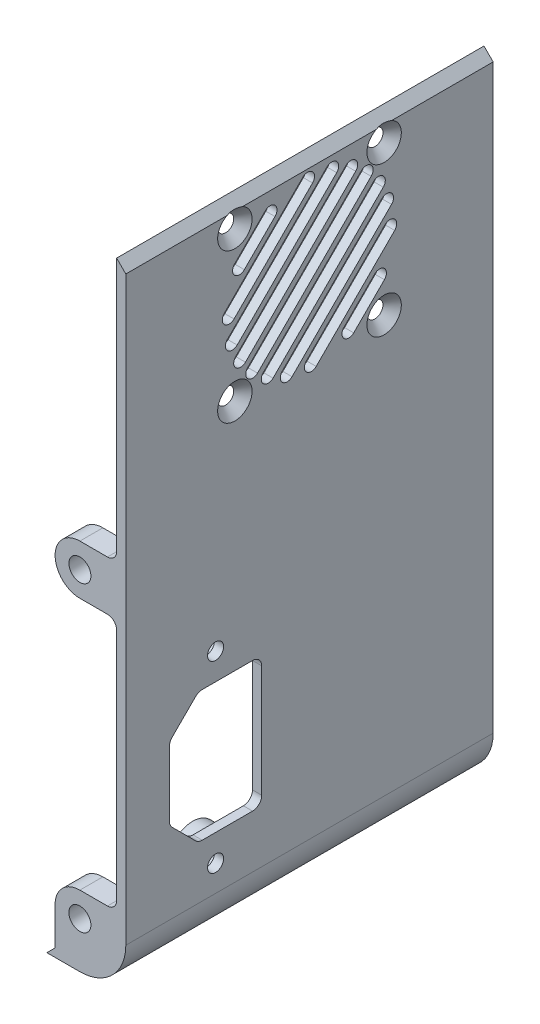
SolidWorks part; units mm, degrees
ref_plane "Piano frontale" through (0, 0, 0) normal (0, 0, 1) x (1, 0, 0)
ref_plane "Piano superiore" through (0, 0, 0) normal (0, 1, 0) x (1, 0, 0)
ref_plane "Piano destro" through (0, 0, 0) normal (1, 0, 0) x (0, 0, -1)
sketch "Schizzo1" plane through (0, 0, 0) normal (0, 0, 1) x (1, 0, 0)
  line L0 (0, 0) -> (170, 0)
  line L1 (170, 0) -> (170, 150)
  line L2 (170, 150) -> (56.5685, 150)
  line L3 (56.5685, 150) -> (0, 93.4315)
  line L4 (0, 93.4315) -> (0, 0)
  dimension "D1" = 45
  dimension "D2" = 170
  dimension "D3" = 150
  dimension "D4" = 80
extrude "Estrusione-Sottile1" add sketch "Schizzo1" along normal blind 80 thin thin type one direction wall 2
ref_plane "middle" through (0, 0, 40) normal (0, 0, -1) x (-1, 0, 0)
sketch "Schizzo2" plane through (-48.1299, 48.1299, 0) normal (-0.7071, 0.7071, 0) x (0, 0, 1)
  line L0 (0, 146.8944) -> (80, 65.2376) construction
  line L2 (13, 88.316) -> (67, 88.316)
  line L3 (13, 88.316) -> (13, 123.816)
  line L4 (13, 123.816) -> (67, 123.816)
  line L5 (67, 88.316) -> (67, 123.816)
  line L6 (13, 88.316) -> (67, 123.816) construction
  line L7 (13, 123.816) -> (67, 88.316) construction
  point P4 (40, 106.066)
  dimension "D1" = 54
  dimension "D2" = 35.5
extrude "Taglio-Estrusione1" cut sketch "Schizzo2" against normal blind 10
fillet "Raccordo1" radius 10 10 edges at (170, 150, 40) (56.5685, 150, 40) (0, 93.4315, 40) (0, 0, 40) (170, 0, 40) (-2, 94.2599, 40) (172, 152, 40) (172, -2, 40) (-2, -2, 40) (55.7401, 152, 40)
sketch "Schizzo3" plane through (-48.1299, 48.1299, 0) normal (-0.7071, 0.7071, 0) x (0, 0, 1)
  line L0 (64.31, 108.816) -> (15.69, 108.816) construction
  line L1 (64.31, 97.666) -> (64.31, 119.966) construction
  line L2 (15.69, 119.966) -> (15.69, 97.666) construction
  line L3 (69, 86.316) -> (11, 86.316)
  line L4 (15.69, 96.666) -> (64.31, 96.666)
  line L5 (15.69, 96.666) -> (15.69, 120.966)
  line L6 (15.69, 120.966) -> (64.31, 120.966)
  line L7 (64.31, 96.666) -> (64.31, 120.966)
  line L8 (15.69, 96.666) -> (64.31, 120.966) construction
  line L9 (15.69, 120.966) -> (64.31, 96.666) construction
  line L10 (67, 123.816) -> (13, 123.816) construction
  line L11 (67, 123.816) -> (67, 88.316) construction
  line L12 (67, 88.316) -> (13, 88.316) construction
  line L13 (13, 123.816) -> (13, 88.316) construction
  line L14 (11, 125.816) -> (11, 86.316)
  line L15 (69, 125.816) -> (11, 125.816)
  line L16 (69, 125.816) -> (69, 86.316)
  point P6 (40, 108.816)
  dimension "D1" = 2
extrude "Estrusione-Estrusione1" add sketch "Schizzo3" along normal blind 1
fillet "Raccordo2" radius 2 8 edges at (12.5511, 109.5181, 11) (40.4819, 137.4489, 11) (40.4819, 137.4489, 69) (12.5511, 109.5181, 69) (37.0524, 134.0194, 64.31) (19.8697, 116.8367, 15.69) (19.8697, 116.8367, 64.31) (37.0524, 134.0194, 15.69)
fillet "Raccordo3" radius 0.5 16 edges at (12.6118, 110.2859, 11.5858) (26.163, 123.837, 11) (39.7141, 137.3882, 11.5858) (40.1283, 137.8024, 40) (39.7141, 137.3882, 68.4142) (26.163, 123.837, 69) (12.6118, 110.2859, 68.4142) (13.3189, 109.5788, 11.5858) (26.8701, 123.1299, 11) (40.4212, 136.6811, 11.5858) (40.8354, 137.0953, 40) (40.4212, 136.6811, 68.4142) (26.8701, 123.1299, 69) (13.3189, 109.5788, 68.4142) (12.1976, 109.8717, 40) (12.9047, 109.1646, 40)
chamfer "Smusso1" distance 0.75 angle 69 8 edges at (36.6988, 134.3729, 40) (36.2846, 133.9587, 16.2758) (36.2846, 133.9587, 63.7242) (28.1075, 125.7816, 15.69) (28.1075, 125.7816, 64.31) (19.9304, 117.6045, 16.2758) (19.9304, 117.6045, 63.7242) (19.5161, 117.1902, 40) first distance on face at (37.0524, 134.0194, 40) first distance on face at (36.4917, 133.4587, 16.4829) first distance on face at (36.4917, 133.4587, 63.5171) first distance on face at (28.461, 125.428, 15.69) first distance on face at (28.461, 125.428, 64.31) first distance on face at (20.4304, 117.3974, 16.4829) first distance on face at (20.4304, 117.3974, 63.5171) first distance on face at (19.8697, 116.8367, 40)
sketch "Schizzo4" plane through (-48.837, 48.837, 0) normal (-0.7071, 0.7071, 0) x (0.7071, 0.7071, 0)
  line L0 (89.316, -11.5) -> (89.316, -68.5) construction
  line L1 (123.816, -11.5) -> (88.316, -11.5) construction
  line L2 (88.316, -68.5) -> (123.816, -68.5) construction
  line L3 (86.816, -13) -> (86.816, -67) construction
  text T0 "Soldering station V3" font "Eras Bold ITC" height 3
  dimension "D1" = 2.5
extrude "Taglio-Estrusione2" cut sketch "Schizzo4" against normal blind 0.75
sketch "Schizzo5" plane through (0, 0, 80) normal (0, 0, 1) x (1, 0, 0)
  line L0 (156.6, 142) -> (156.6, 150)
  line L1 (160, 150) -> (60.7107, 150) construction
  line L2 (162, 136.6) -> (170, 136.6)
  line L3 (170, 10) -> (170, 140) construction
  line L4 (160, 150) -> (156.6, 150)
  line L5 (170, 136.6) -> (170, 140)
  line L6 (162, 13.4) -> (170, 13.4)
  line L7 (170, 13.4) -> (170, 10)
  line L8 (156.6, 8) -> (156.6, 0)
  line L9 (156.6, 0) -> (160, 0)
  line L10 (13.4, 8) -> (13.4, 0)
  line L11 (10, 0) -> (160, 0) construction
  line L12 (13.4, 0) -> (10, 0)
  line L13 (8, 13.4) -> (0, 13.4)
  line L14 (0, 89.2893) -> (0, 10) construction
  line L15 (0, 13.4) -> (0, 10)
  line L16 (6.1615, 99.593) -> (11.8184, 93.9361)
  line L17 (53.6396, 147.0711) -> (2.9289, 96.3604) construction
  line L18 (8, 84.7177) -> (0, 84.7177)
  line L19 (0, 84.7177) -> (0, 89.2893)
  line L20 (6.1615, 99.593) -> (2.9289, 96.3604)
  line L21 (65.2823, 142) -> (65.2823, 150)
  line L22 (65.2823, 150) -> (60.7107, 150)
  line L23 (50.407, 143.8385) -> (56.0639, 138.1816)
  line L24 (50.407, 143.8385) -> (53.6396, 147.0711)
  line L25 (78.4818, 8) -> (78.4818, 0)
  line L26 (89.2818, 8) -> (89.2818, 0)
  line L27 (89.2818, 0) -> (78.4818, 0)
  line L28 (162, 79.2294) -> (170, 79.2294)
  line L29 (162, 68.4294) -> (170, 68.4294)
  line L30 (170, 79.2294) -> (170, 68.4294)
  circle A0 centre (162, 142) radius 2.4
  arc A1 (156.6, 142) -> (162, 136.6) centre (162, 142) ccw
  arc A2 (170, 140) -> (160, 150) centre (160, 140) ccw construction
  arc A3 (170, 140) -> (160, 150) centre (160, 140) ccw
  circle A4 centre (162, 8) radius 2.4
  arc A5 (162, 13.4) -> (156.6, 8) centre (162, 8) ccw
  arc A6 (160, 0) -> (170, 10) centre (160, 10) ccw construction
  arc A7 (160, 0) -> (170, 10) centre (160, 10) ccw
  circle A8 centre (8, 8) radius 2.4
  arc A10 (13.4, 8) -> (8, 13.4) centre (8, 8) ccw
  arc A11 (0, 10) -> (10, 0) centre (10, 10) ccw construction
  arc A12 (0, 10) -> (10, 0) centre (10, 10) ccw
  circle A13 centre (8, 90.1177) radius 2.4
  arc A14 (8, 84.7177) -> (11.8184, 93.9361) centre (8, 90.1177) ccw
  arc A15 (2.9289, 96.3604) -> (0, 89.2893) centre (10, 89.2893) ccw construction
  arc A16 (2.9289, 96.3604) -> (0, 89.2893) centre (10, 89.2893) ccw
  circle A17 centre (59.8823, 142) radius 2.4
  arc A18 (56.0639, 138.1816) -> (65.2823, 142) centre (59.8823, 142) ccw
  arc A19 (60.7107, 150) -> (53.6396, 147.0711) centre (60.7107, 140) ccw construction
  arc A20 (60.7107, 150) -> (53.6396, 147.0711) centre (60.7107, 140) ccw
  circle A21 centre (83.8818, 8) radius 2.4
  arc A22 (89.2818, 8) -> (78.4818, 8) centre (83.8818, 8) ccw
  circle A23 centre (162, 73.8294) radius 2.4
  arc A24 (162, 79.2294) -> (162, 68.4294) centre (162, 73.8294) ccw
  dimension "D1" = 4.8
  dimension "D2" = 3
extrude "Estrusione-Estrusione2" add sketch "Schizzo5" against normal blind 5
fillet "Raccordo4" radius 2 14 edges at (6.1615, 99.593, 77.5) (0, 84.7177, 77.5) (0, 13.4, 77.5) (13.4, 0, 77.5) (78.4818, 0, 77.5) (89.2818, 0, 77.5) (156.6, 0, 77.5) (170, 13.4, 77.5) (170, 68.4294, 77.5) (170, 79.2294, 77.5) (170, 136.6, 77.5) (156.6, 150, 77.5) (50.407, 143.8385, 77.5) (65.2823, 150, 77.5)
mirror "Specchia1" about plane through (0, 0, 40) normal (0, 0, -1) of "Estrusione-Estrusione2", "Raccordo4"
sketch "Schizzo6" plane through (-2, 0, 0) normal (-1, 0, 0) x (0, 0, 1)
  line L0 (40, 90.1177) -> (40, 8) construction
  line L1 (80, 90.1177) -> (0, 90.1177) construction
  line L2 (0, 8) -> (80, 8) construction
  line L4 (11, 13.25) -> (24, 13.25)
  line L5 (11, 13.25) -> (11, 32.75)
  line L6 (11, 32.75) -> (24, 32.75)
  line L7 (24, 13.25) -> (24, 32.75)
  line L8 (11, 13.25) -> (24, 32.75) construction
  line L9 (11, 32.75) -> (24, 13.25) construction
  circle A0 centre (40, 65.1177) radius 3.25
  circle A1 centre (40, 23) radius 6
  point P10 (17.5, 23)
  dimension "D2" = 6.5
  dimension "D4" = 12
  dimension "D1" = 25
  dimension "D3" = 15
  dimension "D5" = 13
  dimension "D6" = 19.5
  dimension "D7" = 22.5
extrude "Taglio-Estrusione3" cut sketch "Schizzo6" against normal blind 5
sketch "Schizzo7" plane through (0, 0, 0) normal (1, 0, 0) x (0, 0, -1)
  line L0 (-71.85, 34.17) -> (-71.85, 25.83) construction
  line L1 (-72.205, 34.17) -> (-71.495, 34.17) construction
  line L2 (-71.495, 25.83) -> (-72.205, 25.83) construction
  line L3 (-71.495, 25.53) -> (-72.205, 25.53) construction
  line L4 (-70.245, 33.22) -> (-70.245, 26.78) construction
  line L5 (-71.495, 25.53) -> (-72.205, 25.53) construction
  line L6 (-71.495, 34.47) -> (-72.205, 34.47) construction
  line L7 (-72.205, 34.47) -> (-71.495, 34.47) construction
  line L8 (-73.455, 33.22) -> (-73.455, 26.78) construction
  line L9 (-71.495, 25.03) -> (-72.205, 25.03)
  line L10 (-73.955, 33.22) -> (-73.955, 26.78)
  line L11 (-71.495, 34.97) -> (-72.205, 34.97)
  line L12 (-69.745, 33.22) -> (-69.745, 26.78)
  arc A0 (-70.245, 26.78) -> (-71.495, 25.53) centre (-71.495, 26.78) cw construction
  arc A1 (-70.245, 33.22) -> (-71.495, 34.47) centre (-71.495, 33.22) ccw construction
  arc A2 (-73.455, 33.22) -> (-72.205, 34.47) centre (-72.205, 33.22) cw construction
  arc A3 (-73.455, 26.78) -> (-72.205, 25.53) centre (-72.205, 26.78) ccw construction
  arc A4 (-73.955, 26.78) -> (-72.205, 25.03) centre (-72.205, 26.78) ccw
  arc A5 (-73.955, 33.22) -> (-72.205, 34.97) centre (-72.205, 33.22) cw
  arc A6 (-69.745, 33.22) -> (-71.495, 34.97) centre (-71.495, 33.22) ccw
  arc A7 (-69.745, 26.78) -> (-71.495, 25.03) centre (-71.495, 26.78) cw
  circle A8 centre (-69.35, 43) radius 2.25
  circle A9 centre (-69.35, 54) radius 2.25
  point P19 (-71.85, 25.53)
  point P28 (-71.85, 34.47)
  dimension "D2" = 4.5
  dimension "D1" = 0.5
extrude "Taglio-Estrusione4" cut sketch "Schizzo7" against normal blind 5
sketch "Schizzo8" plane through (0, 0, 0) normal (1, 0, 0) x (0, 0, -1)
  line L0 (-72.205, 25.03) -> (-71.495, 25.03) construction
  line L1 (-73.955, 33.22) -> (-73.955, 26.78) construction
  line L2 (-71.495, 34.97) -> (-72.205, 34.97) construction
  line L3 (-69.745, 26.78) -> (-69.745, 33.22) construction
  line L4 (-72.205, 25.03) -> (-71.495, 25.03)
  line L5 (-73.955, 33.22) -> (-73.955, 26.78)
  line L6 (-71.495, 34.97) -> (-72.205, 34.97)
  line L7 (-69.745, 26.78) -> (-69.745, 33.22)
  line L8 (-71.495, 36.47) -> (-72.205, 36.47)
  line L9 (-75.455, 33.22) -> (-75.455, 26.78)
  line L10 (-72.205, 23.53) -> (-71.495, 23.53)
  line L11 (-68.245, 26.78) -> (-68.245, 33.22)
  arc A0 (-71.495, 25.03) -> (-69.745, 26.78) centre (-71.495, 26.78) ccw construction
  arc A1 (-73.955, 26.78) -> (-72.205, 25.03) centre (-72.205, 26.78) ccw construction
  arc A2 (-72.205, 34.97) -> (-73.955, 33.22) centre (-72.205, 33.22) ccw construction
  arc A3 (-69.745, 33.22) -> (-71.495, 34.97) centre (-71.495, 33.22) ccw construction
  arc A4 (-71.495, 25.03) -> (-69.745, 26.78) centre (-71.495, 26.78) ccw
  arc A5 (-73.955, 26.78) -> (-72.205, 25.03) centre (-72.205, 26.78) ccw
  arc A6 (-72.205, 34.97) -> (-73.955, 33.22) centre (-72.205, 33.22) ccw
  arc A7 (-69.745, 33.22) -> (-71.495, 34.97) centre (-71.495, 33.22) ccw
  arc A8 (-68.245, 33.22) -> (-71.495, 36.47) centre (-71.495, 33.22) ccw
  arc A9 (-72.205, 36.47) -> (-75.455, 33.22) centre (-72.205, 33.22) ccw
  arc A10 (-75.455, 26.78) -> (-72.205, 23.53) centre (-72.205, 26.78) ccw
  arc A11 (-71.495, 23.53) -> (-68.245, 26.78) centre (-71.495, 26.78) ccw
  dimension "D1" = 1.5
extrude "Estrusione-Estrusione3" add sketch "Schizzo8" along normal up to surface (2 mm away)
chamfer "Smusso2" distance 2 angle 45 8 edges at (-2, 30, 73.955) (-2, 25.5426, 73.4424) (-2, 34.4574, 73.4424) (-2, 25.03, 71.85) (-2, 34.97, 71.85) (-2, 25.5426, 70.2576) (-2, 34.4574, 70.2576) (-2, 30, 69.745)
sketch "Schizzo9" plane through (170, 0, 0) normal (-1, 0, 0) x (0, 0, 1)
  line L0 (52.4, 47.4) -> (63.3787, 47.4) construction
  line L1 (64.4393, 46.9607) -> (69.5607, 41.8393) construction
  line L2 (70, 40.7787) -> (70, 26.6213) construction
  line L3 (69.5607, 25.5607) -> (64.4393, 20.4393) construction
  line L4 (63.3787, 20) -> (52.4, 20) construction
  line L5 (50.9, 21.5) -> (50.9, 45.9) construction
  line L6 (50.9, 45.9) -> (50.9, 21.5) construction
  line L7 (52.4, 47.9) -> (63.3787, 47.9)
  line L8 (64.7929, 47.3142) -> (69.9142, 42.1929)
  line L9 (70.5, 40.7787) -> (70.5, 26.6213)
  line L10 (69.9142, 25.2071) -> (64.7929, 20.0858)
  line L11 (63.3787, 19.5) -> (52.4, 19.5)
  line L12 (50.4, 21.5) -> (50.4, 45.9)
  line L13 (40, 140) -> (40, 135) construction
  line L14 (75, 140) -> (5, 140) construction
  line L15 (40, 135) -> (40, 95) construction
  line L17 (23.75, 98.75) -> (56.25, 98.75) construction
  line L18 (23.75, 98.75) -> (23.75, 131.25) construction
  line L19 (23.75, 131.25) -> (56.25, 131.25) construction
  line L20 (56.25, 98.75) -> (56.25, 131.25) construction
  line L21 (23.75, 98.75) -> (56.25, 131.25) construction
  line L22 (23.75, 131.25) -> (56.25, 98.75) construction
  arc A0 (50.9, 21.5) -> (52.4, 20) centre (52.4, 21.5) ccw construction
  arc A1 (52.4, 20) -> (50.9, 21.5) centre (52.4, 21.5) cw construction
  arc A2 (63.3787, 20) -> (64.4393, 20.4393) centre (63.3787, 21.5) ccw construction
  arc A3 (69.5607, 25.5607) -> (70, 26.6213) centre (68.5, 26.6213) ccw construction
  arc A4 (70, 40.7787) -> (69.5607, 41.8393) centre (68.5, 40.7787) ccw construction
  arc A5 (64.4393, 46.9607) -> (63.3787, 47.4) centre (63.3787, 45.9) ccw construction
  arc A6 (52.4, 47.4) -> (50.9, 45.9) centre (52.4, 45.9) ccw construction
  arc A7 (64.7929, 47.3142) -> (63.3787, 47.9) centre (63.3787, 45.9) ccw
  arc A8 (70.5, 40.7787) -> (69.9142, 42.1929) centre (68.5, 40.7787) ccw
  arc A9 (69.9142, 25.2071) -> (70.5, 26.6213) centre (68.5, 26.6213) ccw
  arc A10 (63.3787, 19.5) -> (64.7929, 20.0858) centre (63.3787, 21.5) ccw
  arc A11 (52.4, 19.5) -> (50.4, 21.5) centre (52.4, 21.5) cw
  arc A12 (52.4, 47.9) -> (50.4, 45.9) centre (52.4, 45.9) ccw
  circle A13 centre (60.45, 53.7) radius 1.75
  circle A14 centre (60.45, 13.7) radius 1.75
  circle A15 centre (56.25, 131.25) radius 1.75
  circle A16 centre (23.75, 131.25) radius 1.75
  circle A17 centre (23.75, 98.75) radius 1.75
  circle A18 centre (56.25, 98.75) radius 1.75
  point P62 (40, 115)
  dimension "D6" = 3.5
  dimension "D7" = 3.5
  dimension "D2" = 5
  dimension "D3" = 40
  dimension "D4" = 32.5
  dimension "D5" = 32.5
  dimension "D1" = 0.5
extrude "Taglio-Estrusione5" cut sketch "Schizzo9" against normal blind 10
sketch "Schizzo10" plane through (170, 0, 0) normal (-1, 0, 0) x (0, 0, 1)
  circle A0 centre (60.45, 53.7) radius 2.4
  circle A1 centre (60.45, 53.7) radius 5.4
  circle A2 centre (60.45, 13.7) radius 2.4
  circle A3 centre (60.45, 13.7) radius 5.4
  dimension "D1" = 4.8
  dimension "D2" = 3
extrude "Estrusione-Estrusione4" add sketch "Schizzo10" along normal blind 3
sketch "Schizzo11" plane through (172, 0, 0) normal (1, 0, 0) x (0, 0, -1)
  line L0 (-56.25, 131.25) -> (-23.75, 98.75) construction
  line L1 (-55.256, 123.5735) -> (-48.5735, 130.256) construction
  line L2 (-56.3166, 124.6342) -> (-49.6342, 131.3166)
  line L3 (-54.1953, 122.5129) -> (-47.5129, 129.1953)
  line L4 (-57.4956, 115.3942) -> (-40.3942, 132.4956) construction
  line L5 (-58.5562, 116.4549) -> (-41.4549, 133.5562)
  line L6 (-56.4349, 114.3336) -> (-39.3336, 131.4349)
  line L7 (-56.8113, 110.1388) -> (-35.1388, 131.8113) construction
  line L8 (-57.8719, 111.1995) -> (-36.1995, 132.8719)
  line L9 (-55.7506, 109.0782) -> (-34.0782, 130.7506)
  line L10 (-55.0091, 106.0013) -> (-31.0013, 130.0091) construction
  line L11 (-56.0698, 107.062) -> (-32.062, 131.0698)
  line L12 (-53.9484, 104.9406) -> (-29.9406, 128.9484)
  line L13 (-52.3744, 102.6256) -> (-27.6256, 127.3744) construction
  line L14 (-53.435, 103.6863) -> (-28.6863, 128.435)
  line L15 (-51.3137, 101.565) -> (-26.565, 126.3137)
  line L16 (-53.435, 128.435) -> (-50.2284, 131.6416) construction
  line L17 (-23.75, 131.25) -> (-56.25, 98.75) construction
  line L18 (-48.9987, 99.9909) -> (-24.9909, 123.9987) construction
  line L19 (-47.938, 98.9302) -> (-23.9302, 122.938)
  line L20 (-50.0594, 101.0516) -> (-26.0516, 125.0594)
  line L21 (-44.8612, 98.1887) -> (-23.1887, 119.8612) construction
  line L22 (-43.8005, 97.1281) -> (-22.1281, 118.8005)
  line L23 (-45.9218, 99.2494) -> (-24.2494, 120.9218)
  line L24 (-39.6058, 97.5044) -> (-22.5044, 114.6058) construction
  line L25 (-38.5451, 96.4438) -> (-21.4438, 113.5451)
  line L26 (-40.6664, 98.5651) -> (-23.5651, 115.6664)
  line L27 (-31.4265, 99.744) -> (-24.744, 106.4265) construction
  line L28 (-30.3658, 98.6834) -> (-23.6834, 105.3658)
  line L29 (-32.4871, 100.8047) -> (-25.8047, 107.4871)
  circle A0 centre (-40, 115) radius 19 construction
  arc A1 (-56.3166, 124.6342) -> (-54.1953, 122.5129) centre (-55.256, 123.5735) ccw
  arc A2 (-47.5129, 129.1953) -> (-49.6342, 131.3166) centre (-48.5735, 130.256) ccw
  arc A3 (-58.5562, 116.4549) -> (-56.4349, 114.3336) centre (-57.4956, 115.3942) ccw
  arc A4 (-39.3336, 131.4349) -> (-41.4549, 133.5562) centre (-40.3942, 132.4956) ccw
  arc A5 (-57.8719, 111.1995) -> (-55.7506, 109.0782) centre (-56.8113, 110.1388) ccw
  arc A6 (-34.0782, 130.7506) -> (-36.1995, 132.8719) centre (-35.1388, 131.8113) ccw
  arc A7 (-56.0698, 107.062) -> (-53.9484, 104.9406) centre (-55.0091, 106.0013) ccw
  arc A8 (-29.9406, 128.9484) -> (-32.062, 131.0698) centre (-31.0013, 130.0091) ccw
  arc A9 (-53.435, 103.6863) -> (-51.3137, 101.565) centre (-52.3744, 102.6256) ccw
  arc A10 (-26.565, 126.3137) -> (-28.6863, 128.435) centre (-27.6256, 127.3744) ccw
  arc A11 (-47.938, 98.9302) -> (-50.0594, 101.0516) centre (-48.9987, 99.9909) cw
  arc A12 (-26.0516, 125.0594) -> (-23.9302, 122.938) centre (-24.9909, 123.9987) cw
  arc A13 (-43.8005, 97.1281) -> (-45.9218, 99.2494) centre (-44.8612, 98.1887) cw
  arc A14 (-24.2494, 120.9218) -> (-22.1281, 118.8005) centre (-23.1887, 119.8612) cw
  arc A15 (-38.5451, 96.4438) -> (-40.6664, 98.5651) centre (-39.6058, 97.5044) cw
  arc A16 (-23.5651, 115.6664) -> (-21.4438, 113.5451) centre (-22.5044, 114.6058) cw
  arc A17 (-30.3658, 98.6834) -> (-32.4871, 100.8047) centre (-31.4265, 99.744) cw
  arc A18 (-25.8047, 107.4871) -> (-23.6834, 105.3658) centre (-24.744, 106.4265) cw
  point P8 (-51.9147, 126.9147)
  point P14 (-48.9449, 123.9449)
  point P21 (-45.9751, 120.9751)
  point P28 (-43.0052, 118.0052)
  point P36 (-40, 115)
  point P49 (-36.9948, 111.9948)
  point P56 (-34.0249, 109.0249)
  point P63 (-31.0551, 106.0551)
  point P70 (-28.0853, 103.0853)
  dimension "D1" = 1.5
  dimension "D2" = 1.2
  dimension "D3" = 1.2
  dimension "D4" = 1.2
  dimension "D5" = 1.3
extrude "Taglio-Estrusione6" cut sketch "Schizzo11" against normal blind 10
chamfer "Smusso3" distance 2 angle 45 4 edges at (172, 98.75, 58) (172, 98.75, 25.5) (172, 131.25, 25.5) (172, 131.25, 58)
sketch "Schizzo12" plane through (-46.7157, 46.7157, 0) normal (0.7071, -0.7071, 0) x (0, 0, -1)
  line L12 (-69.5, 124.366) -> (-61.5, 124.366)
  line L13 (-18.7, 128.366) -> (-10.7, 128.366)
  line L14 (-18.7, 128.366) -> (-18.7, 124.366)
  line L15 (-18.7, 124.366) -> (-10.7, 124.366)
  line L16 (-10.7, 128.366) -> (-10.7, 124.366)
  line L17 (-18.7, 128.366) -> (-10.7, 124.366) construction
  line L18 (-18.7, 124.366) -> (-10.7, 128.366) construction
  line L19 (-69.5, 128.366) -> (-61.5, 124.366) construction
  line L20 (-61.5, 128.366) -> (-61.5, 124.366)
  line L21 (-69.5, 128.366) -> (-69.5, 124.366)
  line L22 (-69.5, 124.366) -> (-61.5, 128.366) construction
  line L23 (-69.5, 128.366) -> (-61.5, 128.366)
  line L24 (-69.5, 87.766) -> (-61.5, 83.766) construction
  line L25 (-69.5, 87.766) -> (-61.5, 87.766)
  line L26 (-69.5, 83.766) -> (-61.5, 83.766)
  line L27 (-69.5, 87.766) -> (-69.5, 83.766)
  line L28 (-69.5, 83.766) -> (-61.5, 87.766) construction
  line L29 (-61.5, 87.766) -> (-61.5, 83.766)
  line L30 (-18.7, 87.766) -> (-10.7, 87.766)
  line L31 (-18.7, 87.766) -> (-10.7, 83.766) construction
  line L32 (-10.7, 87.766) -> (-10.7, 83.766)
  line L33 (-18.7, 83.766) -> (-10.7, 83.766)
  line L34 (-18.7, 83.766) -> (-10.7, 87.766) construction
  line L35 (-18.7, 87.766) -> (-18.7, 83.766)
  circle A0 centre (-14.7, 126.366) radius 0.75
  circle A1 centre (-65.5, 126.366) radius 0.75
  circle A2 centre (-65.5, 85.766) radius 0.75
  circle A3 centre (-14.7, 85.766) radius 0.75
  dimension "D3" = 1.5
  dimension "D1" = 4
  dimension "D2" = 8
extrude "Estrusione-Estrusione5" add sketch "Schizzo12" along normal up to surface (2.7 mm away)
sketch "Schizzo13" plane through (0, 0, 0) normal (1, 0, 0) x (0, 0, -1)
  line L0 (-30.8052, 71.5059) -> (-30.8052, 54.5097) construction
  line L1 (-33.0552, 74.0078) -> (-47.6708, 74.0078) construction
  line L2 (-33.0552, 74.0078) -> (-28.5552, 74.0078)
  line L3 (-33.0552, 74.0078) -> (-33.0552, 52.0078)
  line L4 (-33.0552, 52.0078) -> (-28.5552, 52.0078)
  line L5 (-28.5552, 74.0078) -> (-28.5552, 52.0078)
  line L6 (-33.0552, 74.0078) -> (-28.5552, 52.0078) construction
  line L7 (-33.0552, 52.0078) -> (-28.5552, 74.0078) construction
  line L10 (-47.6708, 49.7337) -> (-47.6708, 75.7337) construction
  line L11 (-40.363, 74.0078) -> (-40.363, 57.3538) construction
  line L12 (-47.6708, 52.0078) -> (-52.1708, 52.0078)
  line L13 (-47.6708, 74.0078) -> (-47.6708, 52.0078)
  line L14 (-52.1708, 74.0078) -> (-52.1708, 52.0078)
  line L15 (-47.6708, 74.0078) -> (-52.1708, 74.0078)
  circle A0 centre (-30.8052, 71.5059) radius 0.75
  circle A1 centre (-30.8052, 54.5097) radius 0.75
  circle A2 centre (-49.9208, 54.5097) radius 0.75
  circle A3 centre (-49.9208, 71.5059) radius 0.75
  point P6 (-30.8052, 63.0078)
  dimension "D1" = 1.5
  dimension "D2" = 4.5
  dimension "D3" = 22
extrude "Estrusione-Estrusione6" add sketch "Schizzo13" along normal up to surface (15.858 mm away)
sketch "Schizzo14" plane through (0, 0, 0) normal (0, 0, -1) x (-1, 0, 0)
  line L0 (-170, 134.6) -> (-170, 136.6)
  line L1 (-170, 134.6) -> (-160.959, 134.1401)
  line L2 (-156.6, 8) -> (-156.6, -6.1676)
  line L3 (-170, 136.6) -> (-175.8979, 136.6)
  line L4 (-156.6, -6.1676) -> (28.2502, -16.3185)
  line L5 (28.2502, -16.3185) -> (21.9321, 143.4926)
  line L6 (21.9321, 143.4926) -> (-69.8663, 163.1902)
  line L7 (-69.8663, 163.1902) -> (-185.8223, 155.7571)
  line L8 (-185.8223, 155.7571) -> (-175.8979, 136.6)
  line L9 (-156.6, 8) -> (-127.8443, 63.587)
  line L10 (-127.8443, 63.587) -> (-160.959, 134.1401)
extrude "Taglio-Estrusione7" cut sketch "Schizzo14" against normal through all
sketch "Schizzo15" plane through (0, 0, 0) normal (0, 1, 0) x (1, 0, 0)
  line L0 (156.6, -75) -> (156.6, -5) construction
  line L1 (159.6, -65) -> (153.6, -65)
  line L2 (159.6, -65) -> (159.6, -15)
  line L3 (159.6, -15) -> (153.6, -15)
  line L4 (153.6, -65) -> (153.6, -15)
  line L5 (159.6, -65) -> (153.6, -15) construction
  line L6 (159.6, -15) -> (153.6, -65) construction
  point P0 (156.6, -40)
  dimension "D1" = 6
  dimension "D2" = 50
extrude "Estrusione-Estrusione7" add sketch "Schizzo15" along normal blind 2
chamfer "Smusso4" distance 2 angle 60 1 edges at (159.6, 0, 40) first distance on face at (159.6, 1, 40)
chamfer "Smusso5" distance 2 angle 45 1 edges at (172, 136.6, 40)
sketch "Schizzo16" plane through (0, 0, 80) normal (0, 0, 1) x (1, 0, 0)
  line L0 (156.6, -2) -> (154.8, -2)
  line L1 (154.8, -2) -> (156.6, -0.2)
  line L2 (156.6, 8) -> (156.6, -2) construction
  line L3 (156.6, -0.2) -> (156.6, -2)
  dimension "D1" = 0.2
  dimension "D2" = 0.2
extrude "Estrusione-Estrusione8" add sketch "Schizzo16" against normal up to surface (80 mm away)
equation "\"D3@Schizzo11\"=\"D2@Schizzo11\""
equation "\"D4@Schizzo11\"=\"D2@Schizzo11\""
